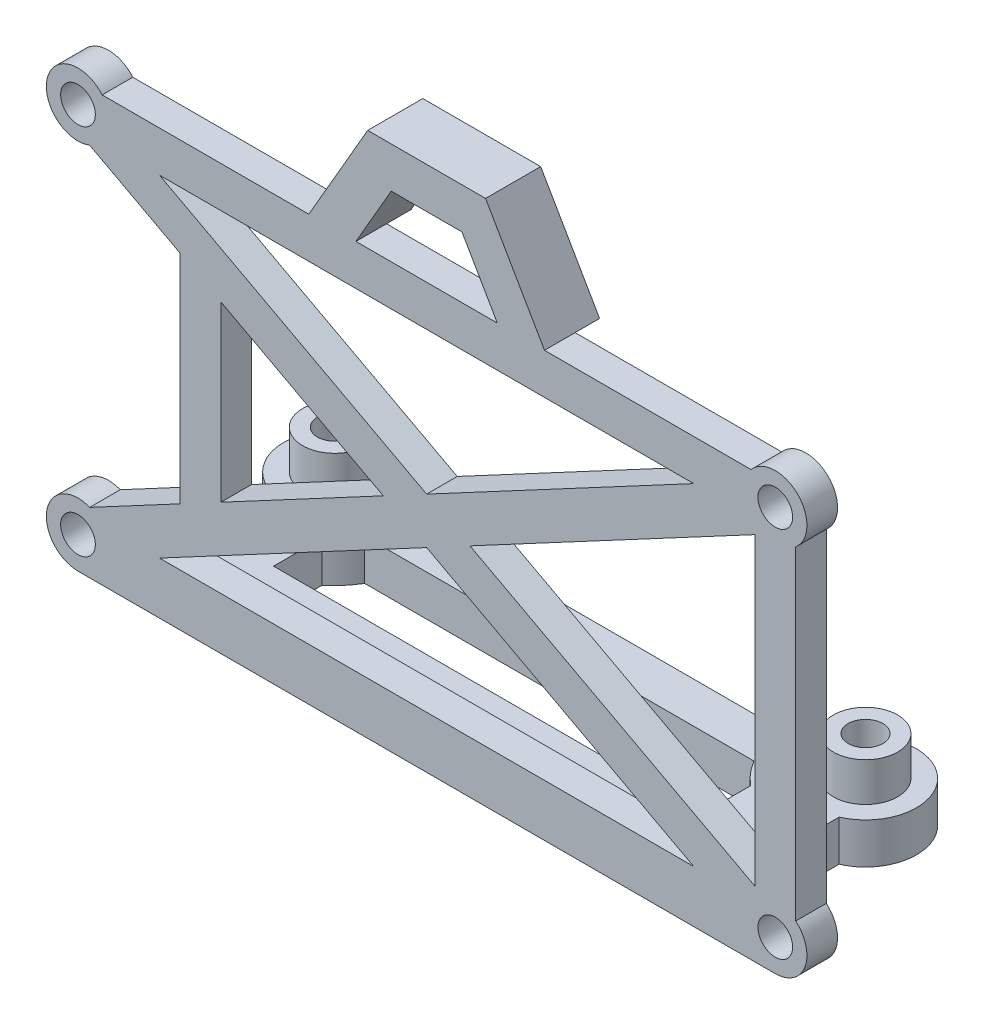
SolidWorks part; units mm, degrees
ref_plane "Front Plane" through (0, 0, 0) normal (0, 0, 1) x (1, 0, 0)
ref_plane "Top Plane" through (0, 0, 0) normal (0, 1, 0) x (1, 0, 0)
ref_plane "Right Plane" through (0, 0, 0) normal (1, 0, 0) x (0, 0, -1)
sketch "Sketch1" plane through (0, 0, 0) normal (0, 0, 1) x (1, 0, 0)
  line L0 (-32.16, 14.9094) -> (-32.16, -14.9094)
  line L1 (-34.16, 18.245) -> (34.16, 18.245) construction
  line L2 (-34.16, 18.245) -> (-34.16, -18.245) construction
  line L3 (-34.16, -18.245) -> (34.16, -18.245) construction
  line L4 (34.16, 18.245) -> (34.16, -18.245) construction
  line L5 (-34.16, 18.245) -> (34.16, -18.245) construction
  line L6 (-34.16, -18.245) -> (34.16, 18.245) construction
  line L7 (-31.7915, 20.245) -> (31.7915, 20.245)
  line L8 (-26.1702, 16.245) -> (0, 2.2674)
  line L9 (-32.16, -14.9094) -> (-4.2452, 0)
  line L10 (36.16, 18.245) -> (36.16, -15.8765)
  line L11 (-26.1702, -16.245) -> (26.1702, -16.245)
  line L12 (-36.16, 15.8765) -> (-36.16, -15.8765)
  line L13 (-26.1702, 16.245) -> (26.1702, 16.245)
  line L14 (-32.16, 14.9094) -> (-4.2452, 0)
  line L15 (-26.1702, -16.245) -> (0, -2.2674)
  line L16 (32.16, 14.9094) -> (32.16, -14.9094)
  line L17 (32.16, 14.9094) -> (33.013, 15.365)
  line L18 (-33.2178, 20.0091) -> (35.1022, -16.4809) construction
  line L19 (-34.16, 20.245) -> (34.16, 20.245) construction
  line L20 (-32.16, 18.245) -> (-32.16, -18.245) construction
  line L21 (-34.16, 16.245) -> (34.16, 16.245) construction
  line L22 (-35.1022, 16.4809) -> (33.2178, -20.0091) construction
  line L23 (-36.16, 18.245) -> (-36.16, -18.245) construction
  line L24 (0, 2.2674) -> (26.1702, 16.245)
  line L25 (-35.1022, -16.4809) -> (33.2178, 20.0091) construction
  line L26 (0, -2.2674) -> (26.1702, -16.245)
  line L27 (4.2452, 0) -> (32.16, -14.9094)
  line L28 (4.2452, 0) -> (32.16, 14.9094)
  line L29 (-33.2178, -20.0091) -> (35.1022, 16.4809) construction
  line L30 (-34.16, -16.245) -> (34.16, -16.245) construction
  line L31 (32.16, -14.9094) -> (33.013, -15.365)
  line L32 (32.16, 18.245) -> (32.16, -18.245) construction
  line L33 (36.16, 18.245) -> (36.16, -18.245) construction
  line L34 (-34.16, -21.345) -> (34.16, -21.345)
  line L35 (-32.16, 14.9094) -> (-33.013, 15.365)
  line L36 (-32.16, -14.9094) -> (-33.013, -15.365)
  line L37 (-22.16, 9.5684) -> (-22.16, -9.5684) construction
  line L38 (-24.16, 9.5684) -> (-24.16, -9.5684) construction
  line L39 (-20.16, 9.5684) -> (-20.16, -9.5684) construction
  line L40 (-24.16, 10.6366) -> (-24.16, -10.6366)
  line L41 (-20.16, 8.5001) -> (-20.16, -8.5001)
  line L42 (6.9282, 20.245) -> (3.4641, 26.245)
  line L43 (11.547, 20.245) -> (5.7735, 30.245)
  line L44 (5.7735, 30.245) -> (-5.7735, 30.245)
  line L45 (-5.7735, 30.245) -> (-11.547, 20.245)
  line L46 (-8.6603, 15.245) -> (-9.2376, 16.245)
  line L48 (9.2376, 16.245) -> (8.6603, 15.245)
  line L49 (0, 10.245) -> (4.3301, 10.245) [skipped]
  line L50 (3.4641, 26.245) -> (-3.4641, 26.245)
  line L51 (-3.4641, 26.245) -> (-6.9282, 20.245)
  line L52 (-3.4641, 26.245) -> (-9.5263, 15.745) construction
  line L53 (8.0829, 18.245) -> (3.4641, 26.245) construction
  line L54 (-5.7735, 30.245) -> (-12.9904, 17.745) construction
  circle A0 centre (-34.16, 18.245) radius 1.7
  circle A1 centre (-34.16, -18.245) radius 1.7
  circle A2 centre (34.16, 18.245) radius 1.7
  circle A3 centre (34.16, -18.245) radius 1.7
  circle A4 centre (-34.16, 18.245) radius 3.1
  circle A5 centre (34.16, 18.245) radius 3.1
  circle A6 centre (34.16, -18.245) radius 3.1
  circle A7 centre (-34.16, -18.245) radius 3.1
  circle A8 centre (-34.16, 18.245) radius 0.3
  circle A9 centre (34.16, 18.245) radius 0.3
  circle A10 centre (34.16, -18.245) radius 0.3
  circle A11 centre (-34.16, -18.245) radius 0.3
  circle A13 centre (0, 20.245) radius 10 construction
  point P0 (0, 0)
  dimension "D3" = 3.4
  dimension "D8" = 20
  dimension "D1" = 68.32
  dimension "D2" = 36.49
  dimension "D10" = 12
  dimension "D4" = 1.4
  dimension "D5" = 1.4
  dimension "D6" = 2
  dimension "D7" = 2
  dimension "D9" = 4
  dimension "D11" = 2
  dimension "D12" = 2
extrude "Boss-Extrude1" add sketch "Sketch1" against normal blind 3 contours A4 A0 | A7 A1 | A5 A2 | A6 A3 | A7 L34 A6 L31 L27 L28 L17 A5 L7 A4 L12 L24 L8 L13 L0 L14 L9 L15 L26 L11 | A6 L10 A5 L17 L16 L31 | L41 L14 L40 L9 | L51 L50 L42 L7 L43 L44 L45 region at (0, -1.3536, 0) region at (-22.2344, 0, 0) region at (-34.6432, 15.2717, 0) region at (-31.6669, -16.5543, 0) region at (-8.4423, 25.1192, 0) region at (31.2016, -18.8124, 0) region at (34.1709, 0, 0) region at (34.6432, 15.2717, 0)
sketch "Sketch2" plane through (0, -21.345, 0) normal (0, -1, 0) x (1, 0, 0)
  line L0 (0, -1000) -> (0, 49000) construction
  line L1 (-34.16, -3) -> (34.16, -3) construction
  line L2 (-28, -12.4174) -> (-28, -3)
  line L3 (28, -12.4174) -> (28, -3)
  line L6 (-19.0718, -13) -> (19.0718, -13)
  line L9 (-21, -17) -> (21, -17)
  line L10 (-28, -3) -> (28, -3)
  line L11 (-21, -6) -> (21, -6)
  line L12 (-21, -6) -> (-21, -10.755)
  line L13 (21, -6) -> (21, -10.755)
  circle A0 centre (-26, -17) radius 1.7
  circle A1 centre (26, -17) radius 1.7
  circle A2 centre (-26, -17) radius 3.15
  circle A3 centre (26, -17) radius 3.15
  circle A4 centre (-26, -17) radius 5
  circle A5 centre (26, -17) radius 5
  arc A6 (-19.0718, -13) -> (-21, -10.755) centre (-26, -17) ccw
  arc A7 (19.0718, -13) -> (21, -10.755) centre (26, -17) cw
  circle A8 centre (-26, -17) radius 8 construction
  circle A9 centre (26, -17) radius 8 construction
  line M9 (-34.16, -3) -> (34.16, -3)
  dimension "D1" = 3.4
  dimension "D2" = 6.3
  dimension "D5" = 10
  dimension "D3" = 52
  dimension "D4" = 14
  dimension "D6" = 56
  dimension "D9" = 4
  dimension "D10" = 3
  dimension "D7" = 3
  dimension "D8" = 3
extrude "Boss-Extrude2" add sketch "Sketch2" against normal blind 4 contours L0 L9 A5 L10 | A5 A3 | A3 A1 | L9 L0 A4 M9 | A4 A2 | A2 A0 region at (-10.5, -21.345, -16.687) region at (0.313, -21.345, -15) region at (-28.6612, -21.345, -21.065) region at (23.3388, -21.345, -12.935) region at (-29.0609, -21.345, -17) region at (22.9391, -21.345, -17)
extrude "Boss-Extrude3" add sketch "Sketch2<3>" against normal blind 3.8 from surface contours A2 A0 | A3 A1 region at (-29.0609, -21.345, -17) region at (22.9391, -21.345, -17) starting at face at (0, -17.345, -9.8884)
sketch "Sketch2<3>" plane through (0, -21.345, 0) normal (0, -1, 0) x (1, 0, 0) same geometry as "Sketch2"
sketch "Sketch3" plane through (0, 0, -3) normal (0, 0, -1) x (-1, 0, 0)
  line L0 (3.4641, 26.245) -> (6.9282, 20.245) construction
  line L1 (-3.4641, 26.245) -> (3.4641, 26.245) construction
  line L2 (-6.9282, 20.245) -> (-3.4641, 26.245) construction
  line L3 (5.7735, 30.245) -> (11.547, 20.245) construction
  line L4 (-5.7735, 30.245) -> (5.7735, 30.245) construction
  line L5 (-11.547, 20.245) -> (-5.7735, 30.245) construction
  line L6 (3.4641, 26.245) -> (6.9282, 20.245)
  line L7 (-3.4641, 26.245) -> (3.4641, 26.245)
  line L8 (-6.9282, 20.245) -> (-3.4641, 26.245)
  line L9 (5.7735, 30.245) -> (11.547, 20.245)
  line L10 (-5.7735, 30.245) -> (5.7735, 30.245)
  line L11 (-11.547, 20.245) -> (-5.7735, 30.245)
  line L12 (-11.547, 20.245) -> (-6.5463, 20.245)
  line L13 (6.9282, 20.245) -> (-6.9282, 20.245) construction
  line L14 (6.9282, 20.245) -> (11.547, 20.245)
  line M18 (-6.9282, 20.245) -> (-3.4641, 26.245)
  line M19 (-3.4641, 26.245) -> (3.4641, 26.245)
  line M20 (3.4641, 26.245) -> (6.9282, 20.245)
  line M29 (11.547, 20.245) -> (5.7735, 30.245)
  line M30 (5.7735, 30.245) -> (-5.7735, 30.245)
  line M31 (-5.7735, 30.245) -> (-11.547, 20.245)
extrude "Boss-Extrude4" add sketch "Sketch3" along normal blind 2.4 contours L14 L12 M20 M29 M30 M31 M18 M19 region at (0, 26.4967, -3)
